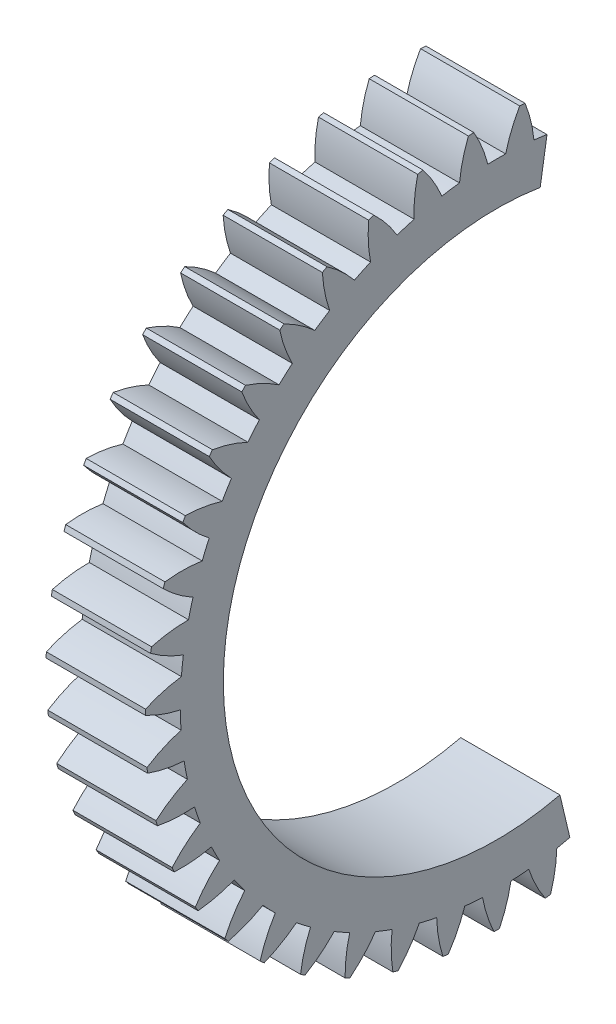
SolidWorks part; units mm, degrees
ref_plane "Plane1" through (0, 0, 0) normal (0, 0, 1) x (1, 0, 0)
ref_plane "Plane2" through (0, 0, 0) normal (0, 1, 0) x (1, 0, 0)
ref_plane "Plane3" through (0, 0, 0) normal (1, 0, 0) x (0, 0, -1)
sketch "HoldingSke" plane through (0, 0, 0) normal (0, 1, 0) x (1, 0, 0)
  line L0 (0, 0) -> (0.4872, -0.1125)
  line L1 (-15, 0) -> (100, 0) construction
  line L2 (0, 0) -> (-2.1039, 2.3779)
  line L3 (0, 0) -> (-11.863, 4.5341)
  line L4 (0, 0) -> (6.316, 5.8897)
  line L5 (0, 0) -> (-23.7986, -8.8762)
  line L6 (0, 0) -> (-10.5278, -7.1032)
  line L7 (-2.1039, 2.3779) -> (8.6589, 51.2073)
  line L8 (-76.2, 54.61) -> (-73.66, 54.61)
  line L9 (-71.009, 38.7566) -> (-53.1078, 45.2721)
  line L10 (-76.2, 71.12) -> (104.1128, 71.12)
  line L11 (0, 0) -> (-12.7, 0)
  line L12 (-76.2, 101.6) -> (-75.9714, 101.6)
  line L13 (24.9733, 27.94) -> (52.9518, 28.4284)
  line L14 (24.9733, 27.94) -> (24.9746, 27.94)
  line L15 (24.9733, 27.94) -> (100.4006, 29.5858)
  line L16 (-63.627, -2) -> (-12.827, -2)
  circle A0 centre (0, 0) radius 35
  circle A1 centre (0, 0) radius 9.4987
  circle A2 centre (0, 0) radius 12.7
  circle A3 centre (0, 0) radius 35
  dimension "Num_teeth" = 43
  dimension "Pitch_radius" = 180.3128
  dimension "Width" = 12.7
  dimension "Thickness" = 12.7
sketch "BasProSke" plane through (0, 0, 0) normal (0, 1, 0) x (1, 0, 0)
  line L0 (-10, 0) -> (60, 0) construction
  line L1 (0, 0) -> (0, 45)
  line L2 (0, 0) -> (12.7, 0)
  line L3 (12.7, 0) -> (12.7, 45)
  line L4 (12.7, 45) -> (0, 45)
  dimension "Thickness" = 12.7
  dimension "Diameter" = 90
revolve "Base-Revolve" add sketch "BasProSke" angle 360 about L0
sketch "TooCutSke" plane through (0, 0, 0) normal (1, 0, 0) x (0, 0, -1)
  line L1 (0, 0) -> (0, 107) construction
  line L2 (0, 0) -> (-1.9704, 42.9548) construction
  line L3 (0, 0) -> (-6.2753, 85.7388) construction
  line L4 (-1.9704, 42.9548) -> (-3.1376, 42.8694) construction
  arc A0 (1.1415, 40.4826) -> (-1.1415, 40.4826) centre (0, 0) ccw
  arc A1 (2.9568, 44.9282) -> (-2.9568, 44.9282) centre (0, 0) ccw
  circle A2 centre (0, 0) radius 43 construction
  circle A3 centre (0, 0) radius 40.4068 construction
  arc A4 (-1.1415, 40.4826) -> (-2.9568, 44.9282) centre (-17.8168, 36.2667) ccw
  arc A5 (2.9568, 44.9282) -> (1.1415, 40.4826) centre (17.8168, 36.2667) ccw
extrude "ToothCut" cut sketch "TooCutSke" along normal through all
fillet "Breaks" [suppressed] radius 0.04 tangent propagation no
fillet "RootFillets" [suppressed] radius 0.5013
pattern_circular "TeethCuts" count 43 over 360 about axis through (-10, 0, 0) along (1, 0, 0) of "ToothCut", "RootFillets", "Breaks"
sketch "HubNeaOneSke" plane through (0, 0, 0) normal (-1, 0, 0) x (0, 0, 1)
  circle A0 centre (0, 0) radius 9.4987
  dimension "Diameter" = 18.9975
extrude "HubNearOne" [suppressed] add sketch "HubNeaOneSke" along normal blind 37.3015
sketch "HubNeaBotSke" plane through (0, 0, 0) normal (-1, 0, 0) x (0, 0, 1)
  circle A0 centre (0, 0) radius 9.4987
  dimension "Diameter" = 18.9975
extrude "HubNearBoth" [suppressed] add sketch "HubNeaBotSke" along normal blind 18.6508
ref_plane "FarPln" through (12.7, 0, 0) normal (1, 0, 0) x (0, 0, -1)
sketch "HubFarSke" plane through (12.7, 0, 0) normal (1, 0, 0) x (0, 0, -1)
  circle A0 centre (0, 0) radius 9.4987
  dimension "Diameter" = 18.9975
extrude "HubFar" [suppressed] add sketch "HubFarSke" along normal blind 18.6508
sketch "BorSke" plane through (0, 0, 0) normal (1, 0, 0) x (0, 0, -1)
  circle A0 centre (0, 0) radius 35
  dimension "Diameter" = 70
extrude "Bore" cut sketch "BorSke" along normal mid plane 100.003
sketch "KeySke" plane through (0, 0, 0) normal (1, 0, 0) x (0, 0, -1)
  line L0 (-3.175, 0) -> (-3.175, 37.54)
  line L1 (-3.175, 37.54) -> (3.175, 37.54)
  line L2 (3.175, 37.54) -> (3.175, 0)
  line L3 (0, 0) -> (0, 34) construction
  line L4 (-3.175, 0) -> (3.175, 0)
  dimension "Width" = 6.35
extrude "Keyway" [suppressed] cut sketch "KeySke" along normal mid plane 100.003
pattern_circular "Keyway2" [suppressed] count 2 every 90 about axis through (-10, 0, 0) along (1, 0, 0) reverse direction yes
sketch "Szkic2" plane through (0, 0, 0) normal (1, 0, 0) x (0, 0, -1)
  line L0 (0, 0) -> (10.92, -45.9662)
  line L1 (8.0896, -34.0523) -> (9.8734, -41.5608) construction
  line L2 (10.92, -45.9662) -> (68.2286, -47.9799)
  line L3 (68.2286, -47.9799) -> (54.0532, 56.0743)
  line L4 (54.0532, 56.0743) -> (14.5542, 57.4622)
  line L5 (0, 0) -> (7.4704, 46.3991)
  line L6 (6.9571, 43.2109) -> (5.5634, 34.555) construction
  line L7 (7.4704, 46.3991) -> (14.5542, 57.4622)
  line L8 (0, 0) -> (4.6414, 28.8278)
  line L9 (4.6414, 28.8278) -> (6.2494, -26.3062)
  line L10 (0, 0) -> (6.2494, -26.3062)
  line L11 (0, 0) -> (4.6414, 28.8278) construction
  line L12 (0, 0) -> (6.2494, -26.3062) construction
  dimension "D1" = 120.619
  dimension "D2" = 99.77
  dimension "D3" = 105.0154
  dimension "D4" = 105.376
  dimension "D5" = 156.515
  dimension "D6" = 169.183
  dimension "D7" = 55.134
  dimension "D8" = 39.5234
  dimension "D9" = 57.344
  dimension "D10" = 13.1367
  dimension "D11" = 46.9966
extrude "Wytnij-wyciągnięcie2" cut sketch "Szkic2" along normal through all contours L5 L9 L0 L2 L3 L4 L7 region at (0, 2.7023, -34.0561)
sketch "Szkic3" plane through (0, 0, 0) normal (1, 0, 0) x (0, 0, -1)
  circle A0 centre (0, 0) radius 45 construction
  circle A1 centre (0, 0) radius 40.4987 construction
  circle A2 centre (0, 0) radius 42.7494 construction
  dimension "D1" = 4.5013
  dimension "D2" = 2.2506
equation "' \"Module@HoldingSke\" = 6.35"
equation "' \"Num_teeth@HoldingSke\" = 12"
equation "' \"Ap@HoldingSke\" =  20"
equation "' \"Ap@HoldingSke\" = 20"
equation "' \"Width@HoldingSke\" = 0.5 * 25.4"
equation "' \"Hub_dia@HoldingSke\"= 1 * 25.4"
equation "' \"Hub_dia@HoldingSke\" = 1 * 25.4"
equation "' \"Overall_len@HoldingSke\" = 1.0 * 25.4"
equation "' \"Bore@HoldingSke\" = 0.75 * 25.4"
equation "' \"T_dim@HoldingSke\" = 0.1 * 25.4"
equation "' \"Width@KeySke\" = 0.25 * 25.4"
equation "' \"Show_teeth@HoldingSke\" = 13"
equation "' \"Backlash@HoldingSke\" = 0.009 * 25.4"
equation "' \"Addendum_fac@HoldingSke\" = 1.0"
equation "' \"Dedendum_fac@HoldingSke\" = 1.25"
equation "' \"Dedendum_add@HoldingSke\" = 0.00005 * 25.4"
equation "' \"Clearance_fac@HoldingSke\" = 0.25"
equation "\"Pitch@HoldingSke\"= 1 / \"Module@HoldingSke\""
equation "\"Overcut_dia@TooCutSke\" = (\"Num_teeth@HoldingSke\" + 2 * \"Addendum_fac@HoldingSke\") / \"Pitch@HoldingSke\" + 0.002 * 25.4"
equation "\"Pitch_dia@TooCutSke\" = \"Num_teeth@HoldingSke\" / \"Pitch@HoldingSke\""
equation "\"Base_dia@TooCutSke\" = \"Num_teeth@HoldingSke\" / \"Pitch@HoldingSke\" * cos((\"Ap@HoldingSke\"  * 3.14159265 / 180))"
equation "\"Root_dia@TooCutSke\" = (\"Num_teeth@HoldingSke\" + 2) / \"Pitch@HoldingSke\" - 2 * (\"Addendum_fac@HoldingSke\" + \"Dedendum_fac@HoldingSke\") / \"Pitch@HoldingSke\" - \"Dedendum_add@HoldingSke\" * 2"
equation "\"Half_ang@TooCutSke\" = 180 / \"Num_teeth@HoldingSke\""
equation "\"Half_CT@TooCutSke\" = \"Num_teeth@HoldingSke\" / \"Pitch@HoldingSke\" * sin((3.14159265 / 2 / \"Num_teeth@HoldingSke\")) / 2 - 7 * \"Backlash@HoldingSke\" / 4"
equation "\"Flank_rad@TooCutSke\" = \"Num_teeth@HoldingSke\" / \"Pitch@HoldingSke\" / 5"
equation "\"Radius@RootFillets\" = \"Clearance_fac@HoldingSke\" / \"Pitch@HoldingSke\" + \"Dedendum_add@HoldingSke\""
equation "\"Break_rad@Breaks\" = 0.02 / \"Pitch@HoldingSke\""
equation "\"Thickness@HoldingSke\" = \"Width@HoldingSke\""
equation "\"OAL@HoldingSke\" = \"Thickness@HoldingSke\""
equation "\"MHD@HoldingSke\" = (\"Num_teeth@HoldingSke\" + 2) / \"Pitch@HoldingSke\" - 2 * (\"Addendum_fac@HoldingSke\" + \"Dedendum_fac@HoldingSke\")  / \"Pitch@HoldingSke\" - \"Dedendum_add@HoldingSke\" * 2"
equation "\"MBD@HoldingSke\" = (\"Num_teeth@HoldingSke\" + 2) / \"Pitch@HoldingSke\" - 2 * (\"Addendum_fac@HoldingSke\" + \"Dedendum_fac@HoldingSke\")  / \"Pitch@HoldingSke\" - \"Dedendum_add@HoldingSke\" * 2 - 0.002 * 25.4"
equation "\"MHD@HoldingSke\" = ((sgn( \"MHD@HoldingSke\" - \"Hub_dia@HoldingSke\" )-1)*( \"MHD@HoldingSke\" - \"Hub_dia@HoldingSke\" ))/-2+ \"Hub_dia@HoldingSke\""
equation "\"MBD@HoldingSke\" = ((sgn( \"MBD@HoldingSke\" - \"Bore@HoldingSke\" )-1)*( \"MBD@HoldingSke\" - \"Bore@HoldingSke\" ))/-2+ \"Bore@HoldingSke\""
equation "\"OAL@HoldingSke\" = ((sgn( \"OAL@HoldingSke\" - \"Overall_len@HoldingSke\" )+1)*( \"OAL@HoldingSke\" - \"Overall_len@HoldingSke\" ))/2 + \"Overall_len@HoldingSke\" + 0.000002 * 25.4"
equation "\"Num_teeth@TeethCuts\" = int( \"Show_teeth@HoldingSke\" ) + 1"
equation "\"Num_teeth@TeethCuts\" = ((sgn( \"Num_teeth@TeethCuts\" - \"Num_teeth@HoldingSke\" )-1)*( \"Num_teeth@TeethCuts\" - \"Num_teeth@HoldingSke\" ))/-2+ \"Num_teeth@HoldingSke\""
equation "\"Num_teeth@TeethCuts\" = ((sgn( \"Num_teeth@TeethCuts\" - 2.0)+1)*( \"Num_teeth@TeethCuts\" - 2.0))/2 +2.0"
equation "\"Angle@TeethCuts\" = 360.0 / \"Num_teeth@HoldingSke\""
equation "\"Diameter@BasProSke\" = (\"Num_teeth@HoldingSke\" + 2 * \"Addendum_fac@HoldingSke\") / \"Pitch@HoldingSke\""
equation "\"Thickness@BasProSke\"  = \"Thickness@HoldingSke\""
equation "' \"Fillet_rad@BasProSke\" =  \"Thickness@HoldingSke\" * 0.05"
equation "' \"Fillet_rad@BasProSke\" = \"Thickness@HoldingSke\" * 0.05"
equation "\"MHD@HoldingSke\" = ((sgn( \"MHD@HoldingSke\" - \"Root_dia@TooCutSke\" )-1)*( \"MHD@HoldingSke\" - \"Root_dia@TooCutSke\" ))/-2+ \"Root_dia@TooCutSke\""
equation "\"Diameter@HubNeaOneSke\" = \"MHD@HoldingSke\""
equation "\"Length@HubNearOne\" = \"OAL@HoldingSke\" - \"Thickness@BasProSke\""
equation "\"Diameter@HubNeaBotSke\" = \"MHD@HoldingSke\""
equation "\"Length@HubNearBoth\" = ( \"OAL@HoldingSke\" - \"Thickness@BasProSke\" ) / 2.0"
equation "\"Thickness@FarPln\" = \"Thickness@BasProSke\""
equation "\"Diameter@HubFarSke\" = \"MHD@HoldingSke\""
equation "\"Length@HubFar\" = ( \"OAL@HoldingSke\" - \"Thickness@BasProSke\" ) / 2.0"
equation "\"Diameter@BorSke\" = \"MBD@HoldingSke\""
equation "\"D1@Bore\" = \"OAL@HoldingSke\" * 2.0"
equation "\"D1@Keyway\" = \"OAL@HoldingSke\" * 2.0"
equation "\"Offset@KeySke\" = \"T_dim@HoldingSke\" + \"MBD@HoldingSke\" / 2.0"
equation "\"D2@Szkic3\"=\"D1@Szkic3\"/2"
